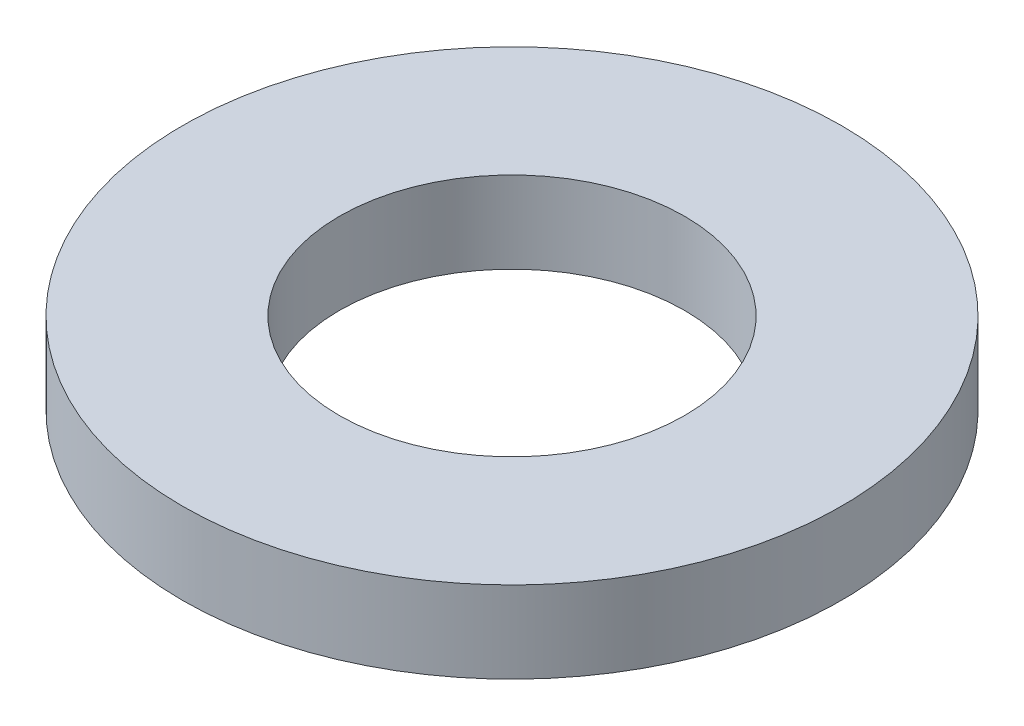
SolidWorks part; units mm, degrees
ref_plane "Front Plane" through (0, 0, 0) normal (0, 0, 1) x (1, 0, 0)
ref_plane "Top Plane" through (0, 0, 0) normal (0, 1, 0) x (1, 0, 0)
ref_plane "Right Plane" through (0, 0, 0) normal (1, 0, 0) x (0, 0, -1)
sketch "Sketch1" plane through (0, 0, 0) normal (0, 1, 0) x (1, 0, 0)
  circle A0 centre (0, 0) radius 52.5
  dimension "FLANGE_OD" = 105
extrude "Boss-Extrude1" add sketch "Sketch1" along normal blind 13
sketch "Sketch2" plane through (0, 0, 0) normal (0, 1, 0) x (1, 0, 0)
  circle A0 centre (0, 0) radius 27.5
  dimension "BORE_D" = 55
extrude "Cut-Extrude1" cut sketch "Sketch2" along normal through all
sketch "Sketch3" plane through (0, 13, 0) normal (0, 1, 0) x (1, 0, 0)
  circle A0 centre (0, 0) radius 19.8459 construction
  circle A1 centre (-19.8459, 0) radius 3.2993
  dimension "BOLT_D" = 6.5985
  dimension "BOLT_PCD" = 39.6917
extrude "Cut-Extrude2" cut sketch "Sketch3" against normal blind 11.6422 rebuild error yes
pattern_circular "CirPattern1" count 5 over 360 rebuild error yes
